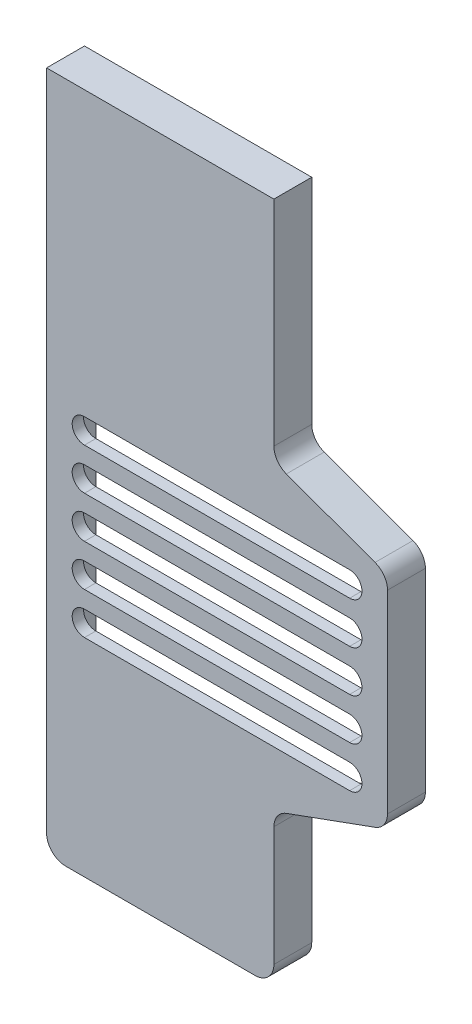
SolidWorks part; units mm, degrees
material "Сплав 2024"
ref_plane "Спереди" through (0, 0, 0) normal (0, 0, 1) x (1, 0, 0)
ref_plane "Сверху" through (0, 0, 0) normal (0, 1, 0) x (1, 0, 0)
ref_plane "Справа" through (0, 0, 0) normal (1, 0, 0) x (0, 0, -1)
sketch "Эскиз1" plane through (0, 0, 0) normal (0, 0, 1) x (1, 0, 0)
  line L0 (31.6276, -80) -> (0, -80) construction
  line L1 (0, 0) -> (60, 0)
  line L2 (0, 0) -> (0, -180)
  line L3 (0, -180) -> (60, -180)
  line L4 (60, 0) -> (60, -60)
  line L5 (30, 0) -> (30, -180) construction
  line L6 (0, -60) -> (-30, -70.9191) construction
  line L7 (-30, -70.9191) -> (-30, -129.0809) construction
  line L8 (-30, -129.0809) -> (0, -140) construction
  line L9 (0, 0) -> (0, -60) construction
  line L10 (0, -140) -> (0, -180) construction
  line L15 (60, -140) -> (60, -180)
  line L16 (90, -129.0809) -> (60, -140)
  line L17 (90, -70.9191) -> (90, -129.0809)
  line L18 (60, -60) -> (90, -70.9191)
  dimension "D1" = 40
  dimension "D2" = 180
  dimension "D3" = 80
  dimension "D4" = 60
  dimension "D5" = 60
  dimension "D6" = 90
  dimension "D7" = 110
  dimension "D8" = 110
extrude "Бобышка-Вытянуть1" add sketch "Эскиз1" along normal blind 10
sketch "Эскиз2" plane through (0, 10, 10) normal (0, 0, 1) x (-1, 0, 0)
  line L0 (-10, 88) -> (-80, 88) construction
  line L1 (-60, 10) -> (0, 10) construction
  line L2 (-30, 190) -> (-30, 10) construction
  line L3 (-10, 102.25) -> (-80, 102.25)
  line L4 (0, 190) -> (-60, 190) construction
  line L5 (0, 10) -> (0, 190) construction
  line L6 (-10, 91.25) -> (-80, 91.25)
  line L7 (-10, 91.25) -> (-10, 84.75) construction
  line L8 (-10, 84.75) -> (-80, 84.75)
  line L9 (-10, 95.75) -> (-80, 95.75)
  line L10 (-80, 91.25) -> (-80, 84.75) construction
  line L11 (-10, 91.25) -> (-80, 84.75) construction
  line L12 (-10, 84.75) -> (-80, 91.25) construction
  line L13 (0, 10) -> (-60, 10) construction
  line L15 (-10, 113.25) -> (-80, 113.25)
  line L16 (-10, 106.75) -> (-80, 106.75)
  line L17 (-10, 124.25) -> (-80, 124.25)
  line L18 (-10, 117.75) -> (-80, 117.75)
  line L19 (-10, 135.25) -> (-80, 135.25)
  line L20 (-10, 128.75) -> (-80, 128.75)
  line L21 (-80, 138.1089) -> (-80, 88) construction
  line L23 (-90, 80.9191) -> (-90, 139.0809) construction
  arc A0 (-10, 91.25) -> (-10, 84.75) centre (-10, 88) cw
  arc A1 (-80, 91.25) -> (-80, 84.75) centre (-80, 88) ccw
  arc A2 (-80, 102.25) -> (-80, 95.75) centre (-80, 99) ccw
  arc A3 (-10, 102.25) -> (-10, 95.75) centre (-10, 99) cw
  arc A4 (-80, 113.25) -> (-80, 106.75) centre (-80, 110) ccw
  arc A5 (-10, 113.25) -> (-10, 106.75) centre (-10, 110) cw
  arc A6 (-80, 124.25) -> (-80, 117.75) centre (-80, 121) ccw
  arc A7 (-10, 124.25) -> (-10, 117.75) centre (-10, 121) cw
  arc A8 (-80, 135.25) -> (-80, 128.75) centre (-80, 132) ccw
  arc A9 (-10, 135.25) -> (-10, 128.75) centre (-10, 132) cw
  point P8 (-45, 88)
  dimension "D3" = 10
  dimension "D1" = 78
  dimension "D2" = 6.5
  dimension "D4" = 10
  dimension "D6" = 50.5
  dimension "D5" = 5
extrude "Вырез-Вытянуть1" cut sketch "Эскиз2" against normal through all
sketch "Эскиз3" plane through (0, 0, 0) normal (0, 0, -1) x (-1, 0, 0)
  line L0 (-60, -140) -> (-60, -180) construction
  line L1 (0, -180) -> (-60, -180) construction
  line L2 (-57, -137.8994) -> (-57, -177)
  line L3 (-60, -60) -> (-90, -70.9191) construction
  line L4 (-90, -70.9191) -> (-90, -129.0809) construction
  line L5 (-90, -129.0809) -> (-60, -140) construction
  line L6 (-3, -62.1006) -> (-3, -177)
  line L7 (0, 0) -> (0, -180) construction
  line L10 (-57, -62.1006) -> (-3, -62.1006)
  line L11 (0, 0) -> (-60, 0) construction
  line L12 (-57, -177) -> (-3, -177)
  line L141 (-87, -73.0197) -> (-87, -126.9803)
  line L142 (-87, -126.9803) -> (-57, -137.8994)
  line L143 (-57, -62.1006) -> (-87, -73.0197)
  dimension "D2" = 3
  dimension "D1" = 3
  dimension "D3" = 3
  dimension "D4" = 3
  dimension "D5" = 3
  dimension "D6" = 3
  dimension "D8" = 62.1006
extrude "Вырез-Вытянуть2" cut sketch "Эскиз3" against normal blind 7
sketch "Эскиз4" plane through (0, 0, 0) normal (0, 0, -1) x (-1, 0, 0)
  line L0 (-30, 0) -> (-30, -180) construction
  line L1 (-40.1, -15) -> (-19.9, -15)
  line L2 (-40.1, -15) -> (-40.1, -64.75)
  line L3 (-40.1, -64.75) -> (-19.9, -64.75)
  line L4 (-19.9, -15) -> (-19.9, -64.75)
  line L5 (-40.1, -15) -> (-19.9, -64.75) construction
  line L6 (-40.1, -64.75) -> (-19.9, -15) construction
  line L7 (0, 0) -> (-60, 0) construction
  line L9 (-80, -74.75) -> (-10, -74.75) construction
  point P0 (-30, -39.875)
  dimension "D1" = 20.2
  dimension "D2" = 15
  dimension "D3" = 10
extrude "Вырез-Вытянуть3" cut sketch "Эскиз4" against normal up to surface (7 mm away) up to face at (45, -89, 7)
sketch "Эскиз6" plane through (0, 0, 0) normal (0, 0, -1) x (-1, 0, 0)
  line L1 (-60, 0) -> (-60, -60) construction
  line L2 (-57, -15) -> (-43.1, -15)
  line L3 (-57, -15) -> (-57, -59.1006)
  line L4 (-57, -59.1006) -> (-43.1, -59.1006)
  line L5 (-43.1, -15) -> (-43.1, -59.1006)
  line L6 (-57, -15) -> (-43.1, -59.1006) construction
  line L8 (-57, -59.1006) -> (-43.1, -15) construction
  line L9 (-40.1, -15) -> (-40.1, -62.1006) construction
  line L11 (-40.1, -62.1006) -> (-57, -62.1006) construction
  line L12 (-19.9, -15) -> (-40.1, -15) construction
  line L13 (-30, 0) -> (-30, -7.5553) construction
  line L14 (-30, 0) -> (-30, -180) construction
  line L15 (-3, -59.1006) -> (-16.9, -15) construction
  line L16 (-3, -15) -> (-16.9, -59.1006) construction
  line L17 (-16.9, -15) -> (-16.9, -59.1006)
  line L18 (-3, -59.1006) -> (-16.9, -59.1006)
  line L19 (-3, -15) -> (-3, -59.1006)
  line L20 (-3, -15) -> (-16.9, -15)
  point P0 (-50.05, -37.0503)
  point P7 (-6.15, -152.5)
  point P8 (-40.1, -38.5503)
  point P13 (-15.69, -152.5)
  point P14 (-25.23, -152.5)
  point P15 (-34.77, -152.5)
  point P16 (-44.31, -152.5)
  point P17 (-48.55, -62.1006)
  point P28 (-9.95, -37.0503)
  dimension "D1" = 3
  dimension "D2" = 3
  dimension "D3" = 3
extrude "Вырез-Вытянуть4" cut sketch "Эскиз6" against normal up to surface (7 mm away) up to face at (42.8182, -88.2093, 7)
fillet "Скругление1" radius 5 25 edges at (60, -60, 5) (90, -70.9191, 5) (90, -129.0809, 5) (60, -140, 5) (0, -180, 5) (60, -180, 5) (57, -15, 3.5) (43.1, -15, 3.5) (57, -59.1006, 3.5) (43.1, -59.1006, 3.5) (40.1, -15, 3.5) (19.9, -15, 3.5) (3, -59.1006, 3.5) (16.9, -59.1006, 3.5) (16.9, -15, 3.5) (3, -15, 3.5) (3, -62.1006, 3.5) (19.9, -62.1006, 3.5) (40.1, -62.1006, 3.5) (57, -62.1006, 3.5) (87, -73.0197, 3.5) (87, -126.9803, 3.5) (3, -177, 3.5) (57, -177, 3.5) (57, -137.8994, 3.5)
equation "\"D6@Эскиз1\"=\"D5@Эскиз1\"+30"
